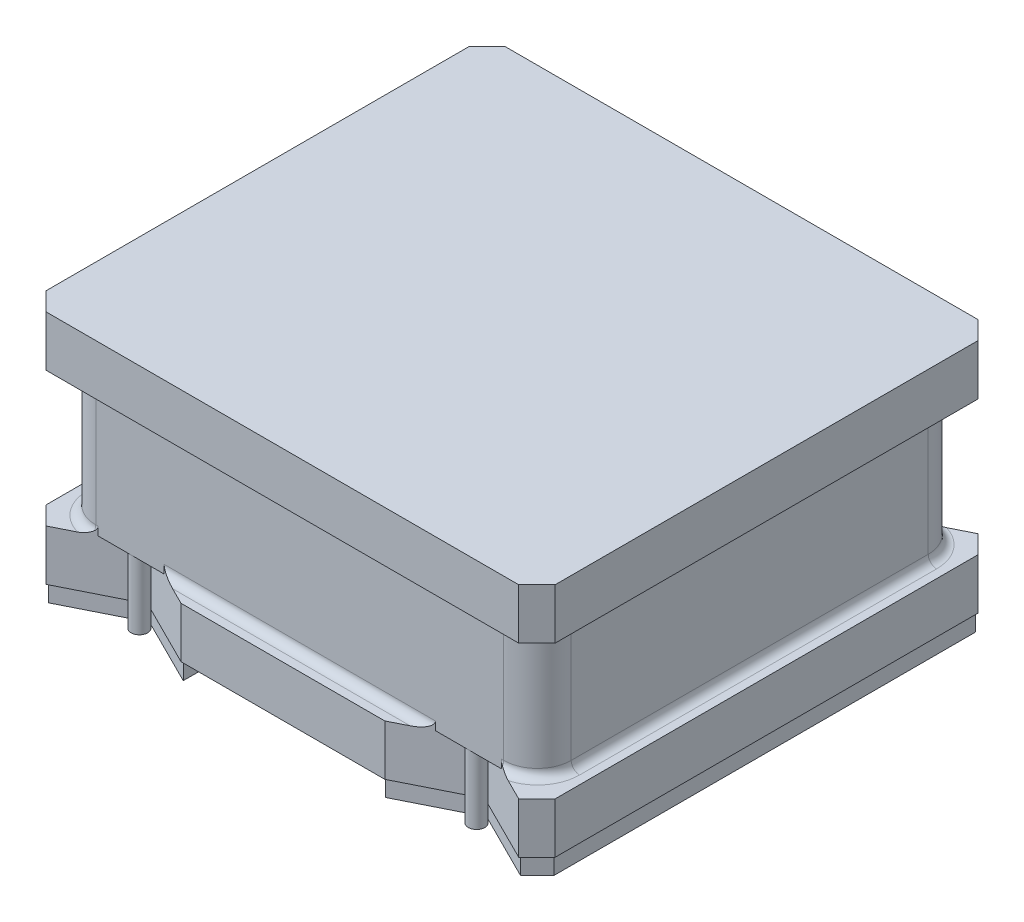
SolidWorks part; units mm, degrees
ref_plane "Plano frontal" through (0, 0, 0) normal (0, 0, 1) x (1, 0, 0)
ref_plane "Plano superior" through (0, 0, 0) normal (0, 1, 0) x (1, 0, 0)
ref_plane "Plano direito" through (0, 0, 0) normal (1, 0, 0) x (0, 0, -1)
sketch "Esboço1" plane through (0, 0, 0) normal (0, 1, 0) x (1, 0, 0)
  line L0 (-1.5, 0) -> (1.945, 0) construction
  line L1 (-1.5, 1.25) -> (-1.5, -1.25)
  line L2 (-1.4, 1.35) -> (-0.6, 1.35) construction
  line L3 (-0.6, -1.35) -> (-0.6, 1.35)
  line L4 (-1, -1.35) -> (-1, -1.15) construction
  line L5 (-1.4, 1.35) -> (-1.5, 1.25)
  line L6 (-1.4, -1.35) -> (-0.6, -1.35) construction
  line L7 (-1, 1.35) -> (-1, 1.15) construction
  line L8 (-1.4, 1.35) -> (-1, 1.15)
  line L9 (-1, 1.15) -> (-0.6, 1.35)
  line L10 (-1, -1.15) -> (-0.6, -1.35)
  line L11 (-1.4, -1.35) -> (-1, -1.15)
  line L12 (-1.4, -1.35) -> (-1.5, -1.25)
  line L13 (0, 1.35) -> (0, -1.35) construction
  line L14 (1, 1.35) -> (1, 1.15) construction
  line L15 (1.4, -1.35) -> (0.6, -1.35) construction
  line L16 (1, -1.35) -> (1, -1.15) construction
  line L17 (1.4, 1.35) -> (0.6, 1.35) construction
  line L18 (1.4, -1.35) -> (1.5, -1.25)
  line L19 (1.4, -1.35) -> (1, -1.15)
  line L20 (1, -1.15) -> (0.6, -1.35)
  line L21 (1, 1.15) -> (0.6, 1.35)
  line L22 (1.4, 1.35) -> (1, 1.15)
  line L23 (1.4, 1.35) -> (1.5, 1.25)
  line L24 (0.6, -1.35) -> (0.6, 1.35)
  line L25 (1.5, 1.25) -> (1.5, -1.25)
  point P3 (-1.5, 1.35)
  point P13 (-1.5, -1.35)
  point P15 (-0.6, 0)
  point P28 (0.6, 0)
  point P29 (1.5, -1.35)
  point P30 (1.5, 1.35)
  dimension "D1" = 1.35
  dimension "D2" = 0.9
  dimension "D3" = 0.6
  dimension "D5" = 135
  dimension "D4" = 0.2
  dimension "D6" = 0.9
extrude "Ressalto-extrusão1" add sketch "Esboço1" along normal blind 0.1
sketch "Esboço2" plane through (0, 0.1, 0) normal (0, 1, 0) x (1, 0, 0)
  line L7 (1.4, 1.35) -> (1, 1.15) construction
  line L10 (1, 1.15) -> (0.6, 1.35) construction
  line L16 (1.5, 1.25) -> (1.4, 1.35) construction
  line L17 (1.5, -1.25) -> (1.5, 1.25) construction
  line L18 (1.4, -1.35) -> (1.5, -1.25) construction
  line L19 (1, -1.15) -> (1.4, -1.35) construction
  line L20 (0.6, -1.35) -> (1, -1.15) construction
  line L21 (-1, -1.15) -> (-0.6, -1.35) construction
  line L22 (-1.4, -1.35) -> (-1, -1.15) construction
  line L23 (-1.5, -1.25) -> (-1.4, -1.35) construction
  line L24 (-1.5, 1.25) -> (-1.5, -1.25) construction
  line L25 (-0.6, 1.35) -> (-1, 1.15) construction
  line L26 (-1, 1.15) -> (-1.4, 1.35) construction
  line L27 (-1.4, 1.35) -> (-1.5, 1.25) construction
  line L120 (-1.4, 1.35) -> (-1.5, 1.25)
  line L121 (-1, 1.15) -> (-1.4, 1.35)
  line L122 (-0.6, 1.35) -> (-1, 1.15)
  line L123 (-1.5, 1.25) -> (-1.5, -1.25)
  line L124 (-1.5, -1.25) -> (-1.4, -1.35)
  line L125 (-1.4, -1.35) -> (-1, -1.15)
  line L126 (-1, -1.15) -> (-0.6, -1.35)
  line L127 (0.6, -1.35) -> (1, -1.15)
  line L128 (1, -1.15) -> (1.4, -1.35)
  line L129 (1.4, -1.35) -> (1.5, -1.25)
  line L130 (1.5, -1.25) -> (1.5, 1.25)
  line L131 (1.5, 1.25) -> (1.4, 1.35)
  line L132 (1, 1.15) -> (0.6, 1.35)
  line L133 (1.4, 1.35) -> (1, 1.15)
  line L134 (-0.6045, 1.3589) -> (-1, 1.1612)
  line L135 (-1, 1.1612) -> (-1.402, 1.3622)
  line L136 (-1.402, 1.3622) -> (-1.51, 1.2541)
  line L137 (-1.51, 1.2541) -> (-1.51, -1.2541)
  line L138 (-1.51, -1.2541) -> (-1.402, -1.3622)
  line L139 (-1.402, -1.3622) -> (-1, -1.1612)
  line L140 (-1, -1.1612) -> (-0.6045, -1.3589)
  line L141 (0.6045, -1.3589) -> (1, -1.1612)
  line L142 (1, -1.1612) -> (1.402, -1.3622)
  line L143 (1.402, -1.3622) -> (1.51, -1.2541)
  line L144 (1.51, -1.2541) -> (1.51, 1.2541)
  line L145 (1.51, 1.2541) -> (1.402, 1.3622)
  line L146 (1.402, 1.3622) -> (1, 1.1612)
  line L147 (1, 1.1612) -> (0.6045, 1.3589)
  line L148 (-0.6045, 1.3589) -> (0.6045, 1.3589)
  line L149 (-0.6045, -1.3589) -> (0.6045, -1.3589)
  line M1 (-0.6, 1.35) -> (-1, 1.15)
  line M2 (-1, 1.15) -> (-1.4, 1.35)
  line M3 (-1.4, 1.35) -> (-1.5, 1.25)
  line M4 (-1.5, 1.25) -> (-1.5, -1.25)
  line M5 (-1.5, -1.25) -> (-1.4, -1.35)
  line M6 (-1.4, -1.35) -> (-1, -1.15)
  line M7 (-1, -1.15) -> (-0.6, -1.35)
  line M8 (-0.6, -1.35) -> (-0.6, 1.35)
  dimension "D1" = 0.01
extrude "Ressalto-extrusão2" add sketch "Esboço2" along normal blind 0.3 contours L140 L149 L141 L142 L143 L144 L145 L146 L147 L148 L134 L135 L136 L137 L138 L139 | M8 M1 M2 M3 M4 M5 M6 M7 region at (-1.0517, 0.1, 0) region at (0.4234, 0.1, 0)
sketch "Esboço3" plane through (0, 0.4, 0) normal (0, 1, 0) x (1, 0, 0)
  line L0 (-0.6045, 1.3589) -> (0.6045, 1.3589) construction
  line L1 (-1.41, 1.2589) -> (1.41, 1.2589)
  line L2 (-1.41, 1.2589) -> (-1.41, -1.2589)
  line L3 (-1.41, -1.2589) -> (1.41, -1.2589)
  line L4 (1.41, 1.2589) -> (1.41, -1.2589)
  line L5 (-1.41, 1.2589) -> (1.41, -1.2589) construction
  line L6 (-1.41, -1.2589) -> (1.41, 1.2589) construction
  line L7 (1.51, -1.2541) -> (1.51, 1.2541) construction
  point P0 (0, 0)
  dimension "D1" = 0.1
  dimension "D2" = 0.1
extrude "Ressalto-extrusão3" add sketch "Esboço3" along normal blind 0.8
sketch "Esboço4" plane through (0, 1.2, 0) normal (0, 1, 0) x (1, 0, 0)
  line L0 (-1.51, 1.2541) -> (-1.402, 1.3622)
  line L1 (-1.402, 1.3622) -> (1.402, 1.3622)
  line L2 (1.402, 1.3622) -> (1.51, 1.2541)
  line L3 (1.51, 1.2541) -> (1.51, -1.2541)
  line L4 (1.51, -1.2541) -> (1.402, -1.3622)
  line L5 (1.402, -1.3622) -> (-1.402, -1.3622)
  line L6 (-1.402, -1.3622) -> (-1.51, -1.2541)
  line L7 (-1.51, -1.2541) -> (-1.51, 1.2541)
extrude "Ressalto-extrusão4" add sketch "Esboço4" along normal blind 0.3
fillet "Filete1" radius 0.2 4 edges at (-1.41, 0.8, -1.2589) (1.41, 0.8, -1.2589) (1.41, 0.8, 1.2589) (-1.41, 0.8, 1.2589)
fillet "Filete2" radius 0.05 8 edges at (1.3514, 1.2, -1.2004) (1.41, 1.2, 0) (1.3514, 1.2, 1.2004) (0, 1.2, 1.2589) (-1.3514, 1.2, 1.2004) (-1.41, 1.2, 0) (-1.3514, 1.2, -1.2004) (0, 1.2, -1.2589)
fillet "Filete3" radius 0.05 12 edges at (-1.2028, 0.4, 1.2589) (-1.3514, 0.4, 1.2004) (-1.41, 0.4, 0) (-1.2028, 0.4, -1.2589) (1.2028, 0.4, 1.2589) (1.3514, 0.4, 1.2004) (1.2028, 0.4, -1.2589) (1.3514, 0.4, -1.2004) (-1.3514, 0.4, -1.2004) (0, 0.4, -1.2589) (1.41, 0.4, 0) (0, 0.4, 1.2589)
sketch "Esboço5" plane through (0, 0.4, 0) normal (0, -1, 0) x (1, 0, 0)
  line L0 (-1, 1.1612) -> (-1, 1.2589) construction
  line L1 (-1.1955, 1.2589) -> (-0.8045, 1.2589) construction
  line L2 (0, 0) -> (0, 1.3589) construction
  line L3 (-0.6045, 1.3589) -> (0.6045, 1.3589) construction
  circle A0 centre (-1, 1.2101) radius 0.0489
  circle A1 centre (1, 1.2101) radius 0.0489
extrude "Ressalto-extrusão5" add sketch "Esboço5" along normal up to surface (0.4 mm away) up to face at (-1.125, 0, 0)
